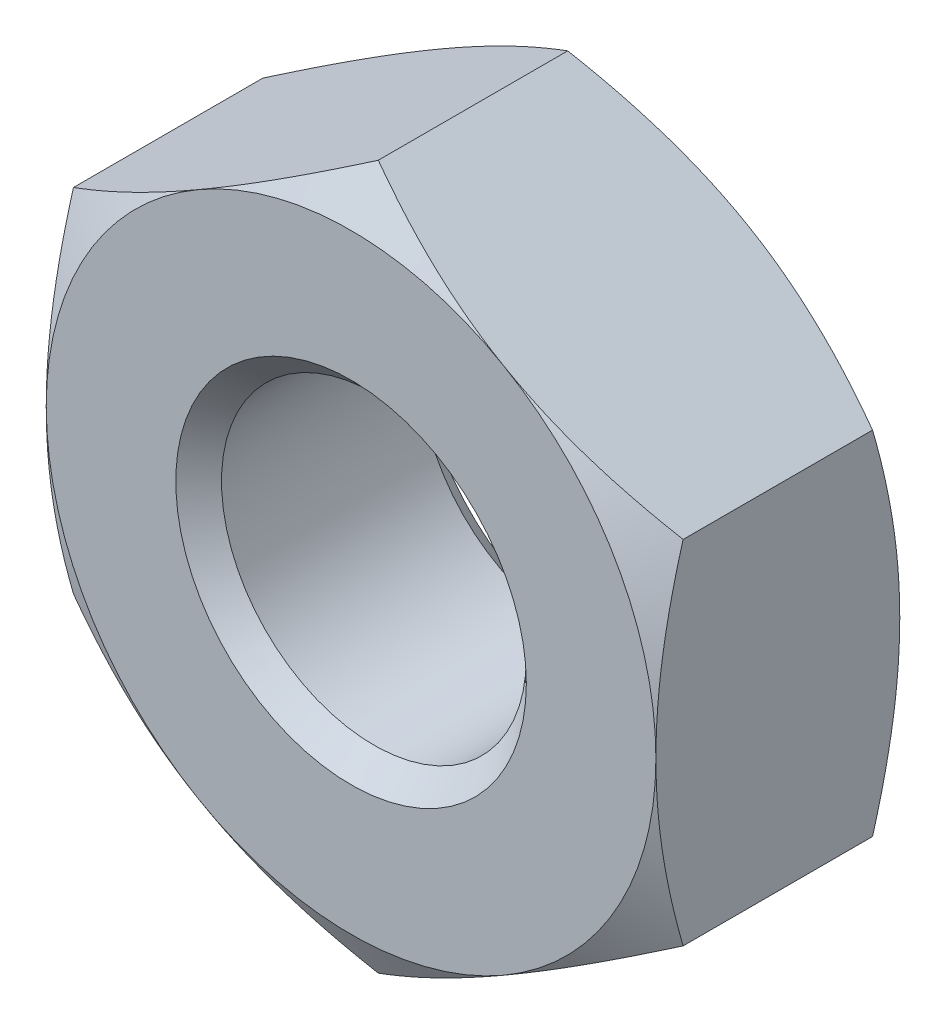
SolidWorks part; units mm, degrees
material "AISI Type A2 Tool Steel"
ref_plane "Front Plane" through (0, 0, 0) normal (0, 0, 1) x (1, 0, 0)
ref_plane "Top Plane" through (0, 0, 0) normal (0, 1, 0) x (1, 0, 0)
ref_plane "Right Plane" through (0, 0, 0) normal (1, 0, 0) x (0, 0, -1)
sketch "Sketch1" plane through (0, 0, 0) normal (0, 0, 1) x (1, 0, 0)
  line L1 (0, 2.3094) -> (-2, 1.1547)
  line L2 (-2, 1.1547) -> (-2, -1.1547)
  line L3 (-2, -1.1547) -> (0, -2.3094)
  line L4 (0, -2.3094) -> (2, -1.1547)
  line L5 (2, -1.1547) -> (2, 1.1547)
  line L6 (2, 1.1547) -> (0, 2.3094)
  circle A0 centre (0, 0) radius 2 construction
  circle A1 centre (0, 0) radius 1
  circle A3 centre (0, 0) radius 3
  dimension "D1" = 6
  dimension "D2" = 4
  dimension "D3" = 2
extrude "Boss-Extrude1" add sketch "Sketch1" along normal blind 1.6 contours A3 L6 L5 L4 L3 L2 L1 | L5 L6 L1 L2 L3 L4 A1 region at (0.9694, 1.6791, 0) region at (-2.9151, 0, 0)
chamfer "Chamfer1" distance 1 angle 30 1 edges at (3, 0, 1.6) first distance on face at (3, 0, 1.6)
chamfer "Chamfer2" distance 1 angle 30 1 edges at (3, 0, 0) first distance on face at (3, 0, 0)
extrude "Cut-Extrude1" cut sketch "Sketch1<3>" along normal through all contours A3 L6 L5 L4 L3 L2 L1 region at (-2.9151, 0, 0)
sketch "Sketch1<3>" plane through (0, 0, 0) normal (0, 0, 1) x (1, 0, 0) same geometry as "Sketch1"
chamfer "Chamfer3" distance 0.15 angle 45 2 edges at (1, 0, 0) (1, 0, 1.6)
